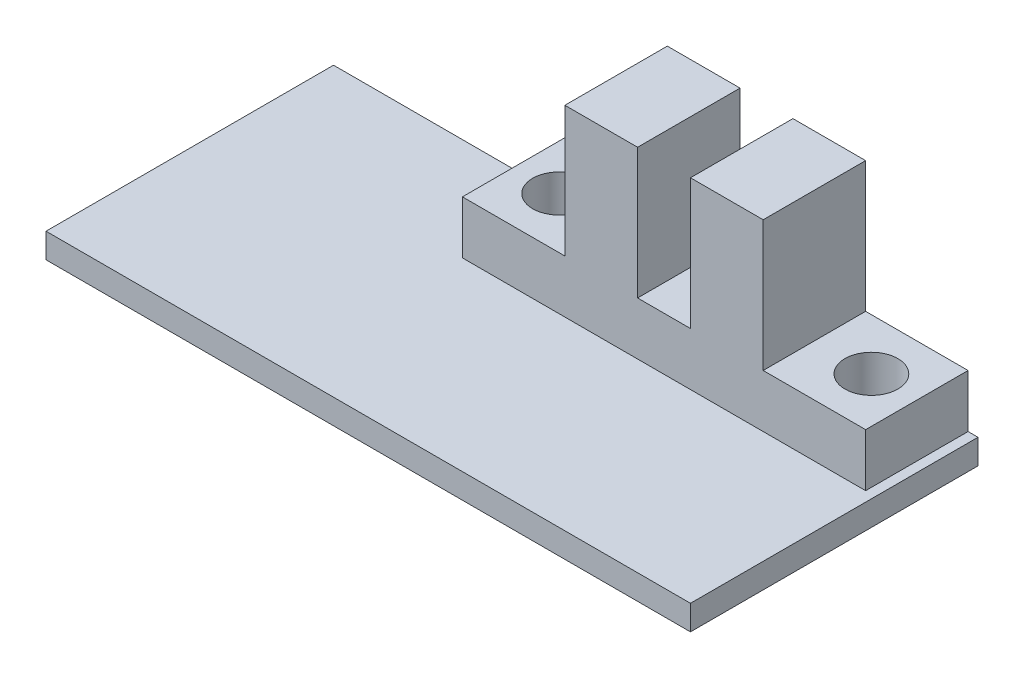
SolidWorks part; units mm, degrees
ref_plane "Front Plane" through (0, 0, 0) normal (0, 0, 1) x (1, 0, 0)
ref_plane "Top Plane" through (0, 0, 0) normal (0, 1, 0) x (1, 0, 0)
ref_plane "Right Plane" through (0, 0, 0) normal (1, 0, 0) x (0, 0, -1)
sketch "Sketch1" plane through (0, 0, 0) normal (0, 1, 0) x (1, 0, 0)
  line L1 (-19.5, 8.7) -> (19.5, 8.7)
  line L2 (-19.5, 8.7) -> (-19.5, -8.7)
  line L3 (-19.5, -8.7) -> (19.5, -8.7)
  line L4 (19.5, 8.7) -> (19.5, -8.7)
  line L5 (-19.5, 8.7) -> (19.5, -8.7) construction
  line L6 (-19.5, -8.7) -> (19.5, 8.7) construction
  point P0 (0, 0)
  dimension "D1" = 39
  dimension "D2" = 17.4
extrude "Boss-Extrude1" add sketch "Sketch1" along normal blind 1.5
sketch "Sketch2" plane through (0, 1.5, 0) normal (0, 1, 0) x (1, 0, 0)
  line L0 (19.5, 8.7) -> (-19.5, 8.7) construction
  line L1 (-5.5, 8.7) -> (18.9, 8.7)
  line L2 (-5.5, 8.7) -> (-5.5, 2.5)
  line L3 (-5.5, 2.5) -> (18.9, 2.5)
  line L4 (18.9, 8.7) -> (18.9, 2.5)
  line L5 (19.5, -8.7) -> (19.5, 8.7) construction
  dimension "D1" = 0.6
  dimension "D2" = 6.2
  dimension "D3" = 24.4
extrude "Boss-Extrude2" add sketch "Sketch2" along normal blind 3.2
sketch "Sketch3" plane through (0, 4.7, 0) normal (0, 1, 0) x (1, 0, 0)
  line L0 (18.9, 8.7) -> (-5.5, 8.7) construction
  line L1 (0.7, 8.7) -> (5.1, 8.7)
  line L2 (0.7, 8.7) -> (0.7, 2.5)
  line L3 (0.7, 2.5) -> (5.1, 2.5)
  line L4 (5.1, 8.7) -> (5.1, 2.5)
  line L5 (-5.5, 2.5) -> (18.9, 2.5) construction
  line L6 (-5.5, 8.7) -> (-5.5, 2.5) construction
  line L7 (8.3, 8.7) -> (12.7, 8.7)
  line L8 (8.3, 8.7) -> (8.3, 2.5)
  line L9 (8.3, 2.5) -> (12.7, 2.5)
  line L10 (12.7, 8.7) -> (12.7, 2.5)
  dimension "D1" = 4.4
  dimension "D2" = 4.4
  dimension "D3" = 12
  dimension "D4" = 6.2
extrude "Boss-Extrude3" add sketch "Sketch3" along normal blind 7.9
sketch "Sketch4" plane through (0, 4.7, 0) normal (0, 1, 0) x (1, 0, 0)
  line L0 (0.7, 8.7) -> (-5.5, 8.7) construction
  line L1 (18.9, 8.7) -> (12.7, 8.7) construction
  line L2 (-5.5, 8.7) -> (-5.5, 2.5) construction
  circle A0 centre (-2.75, 5.6) radius 1.6
  circle A1 centre (16.15, 5.6) radius 1.6
  dimension "D1" = 3.2
  dimension "D3" = 3.2
  dimension "D2" = 3.1
  dimension "D4" = 3.1
  dimension "D5" = 18.9
  dimension "D6" = 2.75
extrude "Cut-Extrude1" cut sketch "Sketch4" against normal through all
